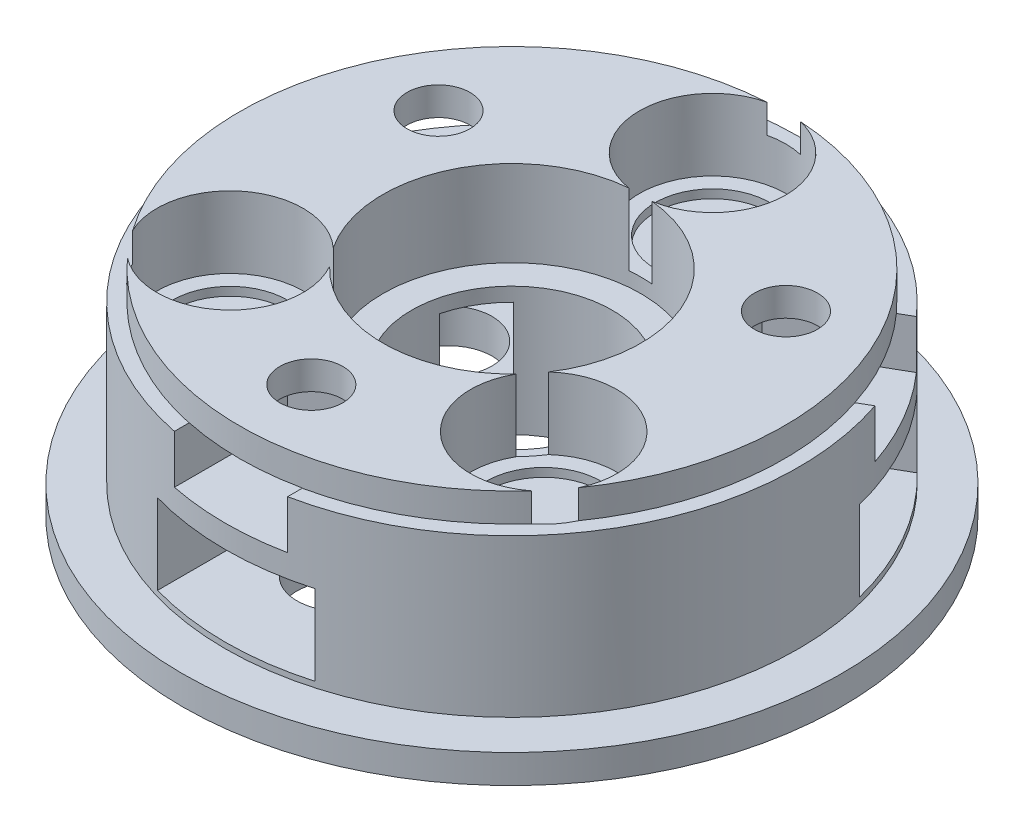
SolidWorks part; units mm, degrees
ref_plane "Front Plane" through (0, 0, 0) normal (0, 0, 1) x (1, 0, 0)
ref_plane "Top Plane" through (0, 0, 0) normal (0, 1, 0) x (1, 0, 0)
ref_plane "Right Plane" through (0, 0, 0) normal (1, 0, 0) x (0, 0, -1)
sketch "Sketch2" plane through (0, 0, 0) normal (0, 1, 0) x (1, 0, 0)
  circle A0 centre (0, 0) radius 11.5
  dimension "D1" = 23
extrude "Boss-Extrude1" add sketch "Sketch2" along normal blind 1
sketch "Sketch3" plane through (0, 1, 0) normal (0, 1, 0) x (1, 0, 0)
  circle A0 centre (0, 0) radius 10
  dimension "D1" = 20
extrude "Boss-Extrude2" add sketch "Sketch3" along normal blind 4
ref_plane "Plane1" through (0, 4.9878, 0) normal (0, -1, 0) x (-1, 0, 0)
sketch "Sketch4" plane through (0, 4.9878, 0) normal (0, -1, 0) x (-1, 0, 0)
  circle A0 centre (0, 0) radius 7 construction
  circle A1 centre (0, 7) radius 2.55
  dimension "D1" = 14
  dimension "D2" = 5.1
extrude "Cut-Extrude1" cut sketch "Sketch4" against normal through all
sketch "Sketch5" plane through (0, 4.9878, 0) normal (0, 1, 0) x (1, 0, 0)
  circle A0 centre (0, 7) radius 2
  dimension "D1" = 4
extrude "Cut-Extrude2" cut sketch "Sketch5" against normal blind 0.3
ref_axis "Axis1" through (0, 5, 0) along (0, -1, 0)
pattern_circular "CirPattern1" count 14 over 360 about axis through (0, 5, 0) along (0, -1, 0) skipping 1, 2, 3, 4, 6, 7, 8, 10, 11, 12, 13 of "Cut-Extrude1", "Cut-Extrude2"
sketch "Sketch7" plane through (0, 4.9878, 0) normal (0, 1, 0) x (1, 0, 0)
  circle A0 centre (5.4728, -4.3644) radius 2.55 construction
  circle A1 centre (0, 0) radius 10
  circle A3 centre (-5.4728, -4.3644) radius 2.55 construction
  circle A4 centre (0, 7) radius 2.55 construction
  circle A5 centre (5.4728, -4.3644) radius 2.55
  circle A6 centre (-5.4728, -4.3644) radius 2.55
  circle A7 centre (0, 7) radius 2.55
  circle A9 centre (0, 0) radius 10
  dimension "D1" = 0
extrude "Boss-Extrude4" add sketch "Sketch7" along normal blind 1.5
sketch "Sketch6" plane through (0, 6.4878, 0) normal (0, 1, 0) x (1, 0, 0)
  circle A0 centre (0, 0) radius 4.5 construction
  arc A1 (-0.5851, 9.482) -> (-0.4025, 4.482) centre (0, 7) ccw
  circle A2 centre (0, 0) radius 9.5 construction
  arc A3 (-3.7551, -2.4798) -> (-7.7781, -5.4545) centre (-5.4728, -4.3644) ccw
  arc A4 (3.2532, -3.1091) -> (7.0485, -6.3694) centre (5.4728, -4.3644) ccw
  arc A5 (0.4025, 4.482) -> (0.5851, 9.482) centre (0, 7) ccw
  arc A6 (-7.0485, -6.3694) -> (-3.2532, -3.1091) centre (-5.4728, -4.3644) ccw
  arc A7 (7.7781, -5.4545) -> (3.7551, -2.4798) centre (5.4728, -4.3644) ccw
  arc A8 (-3.7551, -2.4798) -> (-0.4025, 4.482) centre (0, 0) cw
  arc A9 (-7.7781, -5.4545) -> (-0.5851, 9.482) centre (0, 0) cw
  arc A12 (-3.2532, -3.1091) -> (3.2532, -3.1091) centre (0, 0) ccw
  arc A13 (-7.0485, -6.3694) -> (7.0485, -6.3694) centre (0, 0) ccw
  arc A14 (0.4025, 4.482) -> (3.7551, -2.4798) centre (0, 0) cw
  arc A15 (0.5851, 9.482) -> (7.7781, -5.4545) centre (0, 0) cw
  dimension "D1" = 9
  dimension "D2" = 5.1
  dimension "D3" = 19
extrude "Boss-Extrude3" add sketch "Sketch6" along normal up to surface (0.998 mm away)
sketch "Sketch8" plane through (0, 7.4858, 0) normal (0, 1, 0) x (1, 0, 0)
  circle A0 centre (0, -7) radius 1.1 construction
  circle A1 centre (0, -7) radius 1.1
extrude "Cut-Extrude3" cut sketch "Sketch8" against normal offset from surface (2.69 mm away) 12.2
sketch "Sketch9" plane through (0, 4.7958, 0) normal (0, 1, 0) x (1, 0, 0)
  line L0 (-1.975, -8.1403) -> (-1.975, -11.3291)
  line L1 (0, -9.2805) -> (1.975, -8.1403) construction
  line L2 (1.975, -8.1403) -> (1.975, -5.8597)
  line L3 (1.975, -5.8597) -> (0, -4.7195)
  line L4 (0, -4.7195) -> (-1.975, -5.8597)
  line L5 (-1.975, -5.8597) -> (-1.975, -8.1403)
  line L6 (-1.975, -8.1403) -> (0, -9.2805) construction
  line L7 (-1.975, -11.3291) -> (1.975, -11.3291)
  line L8 (1.975, -11.3291) -> (1.975, -8.1403)
  circle A0 centre (0, -7) radius 1.975 construction
  circle A1 centre (0, 0) radius 11.5 construction
  dimension "D1" = 3.95
extrude "Cut-Extrude4" cut sketch "Sketch9" along normal blind 1.7 contours L7 L8 L2 L3 L4 L5 L0
pattern_circular "CirPattern2" count 3 over 360 about axis through (0, 5, 0) along (0, -1, 0) of "Cut-Extrude4", "Cut-Extrude3"
sketch "Sketch10" plane through (0, 0, 0) normal (0, -1, 0) x (1, 0, 0)
  circle A0 centre (0, 0) radius 8 construction
  circle A1 centre (0, 8) radius 1.35
  dimension "D1" = 16
  dimension "D2" = 2.7
sketch "Sketch11" [suppressed] plane through (0, 0, 0) normal (0, -1, 0) x (1, 0, 0)
  circle A1 centre (0, 0) radius 11.5
  circle A2 centre (0, 0) radius 11.5
  dimension "D1" = 0
extrude "Boss-Extrude5" [suppressed] add sketch "Sketch11" along normal blind 3
sketch "Sketch12" [suppressed] plane through (0, -3, 0) normal (0, -1, 0) x (1, 0, 0)
  circle A0 centre (0, 8) radius 1.65
  dimension "D1" = 3.3
extrude "Cut-Extrude5" [suppressed] cut sketch "Sketch12" against normal up to surface (4 mm away) up to face at (0, 1, 10)
sketch "Sketch13" [suppressed] plane through (0, 1, 0) normal (0, 1, 0) x (1, 0, 0)
  line L0 (-2.75, -9.5877) -> (-2.75, -11.5)
  line L1 (0, -11.1754) -> (2.75, -9.5877) construction
  line L2 (2.75, -9.5877) -> (2.75, -6.4123)
  line L3 (2.75, -6.4123) -> (0, -4.8246)
  line L4 (0, -4.8246) -> (-2.75, -6.4123)
  line L5 (-2.75, -6.4123) -> (-2.75, -9.5877)
  line L6 (-2.75, -9.5877) -> (0, -11.1754) construction
  line L7 (-2.75, -11.5) -> (2.75, -11.5)
  line L8 (2.75, -11.5) -> (2.75, -9.5877)
  circle A0 centre (0, -8) radius 2.75 construction
  circle A1 centre (0, 0) radius 11.5 construction
  dimension "D1" = 5.5
extrude "Cut-Extrude6" [suppressed] cut sketch "Sketch13" against normal blind 2.8
pattern_circular "CirPattern3" [suppressed] count 4 over 360 about axis through (0, 5, 0) along (0, -1, 0) of bodies 114
sketch "Sketch14" plane through (0, 0, 0) normal (0, -1, 0) x (1, 0, 0)
  circle A0 centre (0, 0) radius 6 construction
  circle A1 centre (0, 6) radius 1.5
  dimension "D1" = 12
  dimension "D2" = 3
extrude "Cut-Extrude7" cut sketch "Sketch14" against normal blind 4
sketch "Sketch15" plane through (0, 4, 0) normal (0, -1, 0) x (1, 0, 0)
  line L1 (0, 2.8246) -> (2.75, 4.4123)
  line L2 (2.75, 4.4123) -> (2.75, 7.5877)
  line L3 (2.75, 7.5877) -> (0, 9.1754) construction
  line L4 (0, 9.1754) -> (-2.75, 7.5877) construction
  line L5 (-2.75, 7.5877) -> (-2.75, 4.4123)
  line L6 (-2.75, 4.4123) -> (0, 2.8246)
  line L9 (2.75, 11.5) -> (-2.75, 11.5)
  line L10 (-2.75, 7.5877) -> (-2.75, 11.5)
  line L11 (2.75, 7.5877) -> (2.75, 11.5)
  circle A0 centre (0, 6) radius 2.75 construction
  circle A2 centre (0, 0) radius 11.5 construction
  dimension "D1" = 5.5
extrude "Cut-Extrude8" cut sketch "Sketch15" along normal blind 2.8
pattern_circular "CirPattern4" count 3 over 360 about axis through (0, 5, 0) along (0, -1, 0) of "Cut-Extrude7", "Cut-Extrude8"
sketch "Sketch16" plane through (0, 6.4878, 0) normal (0, 1, 0) x (1, 0, 0)
  circle A0 centre (0, 0) radius 4.5
  arc A1 (3.7551, -2.4798) -> (0.4025, 4.482) centre (0, 0) ccw construction
extrude "Cut-Extrude9" cut sketch "Sketch16" against normal blind 2
sketch "Sketch17" plane through (0, 4.4878, 0) normal (0, 1, 0) x (1, 0, 0)
  circle A0 centre (0, 0) radius 3.5
  dimension "D1" = 7
extrude "Cut-Extrude10" cut sketch "Sketch17" against normal through all
